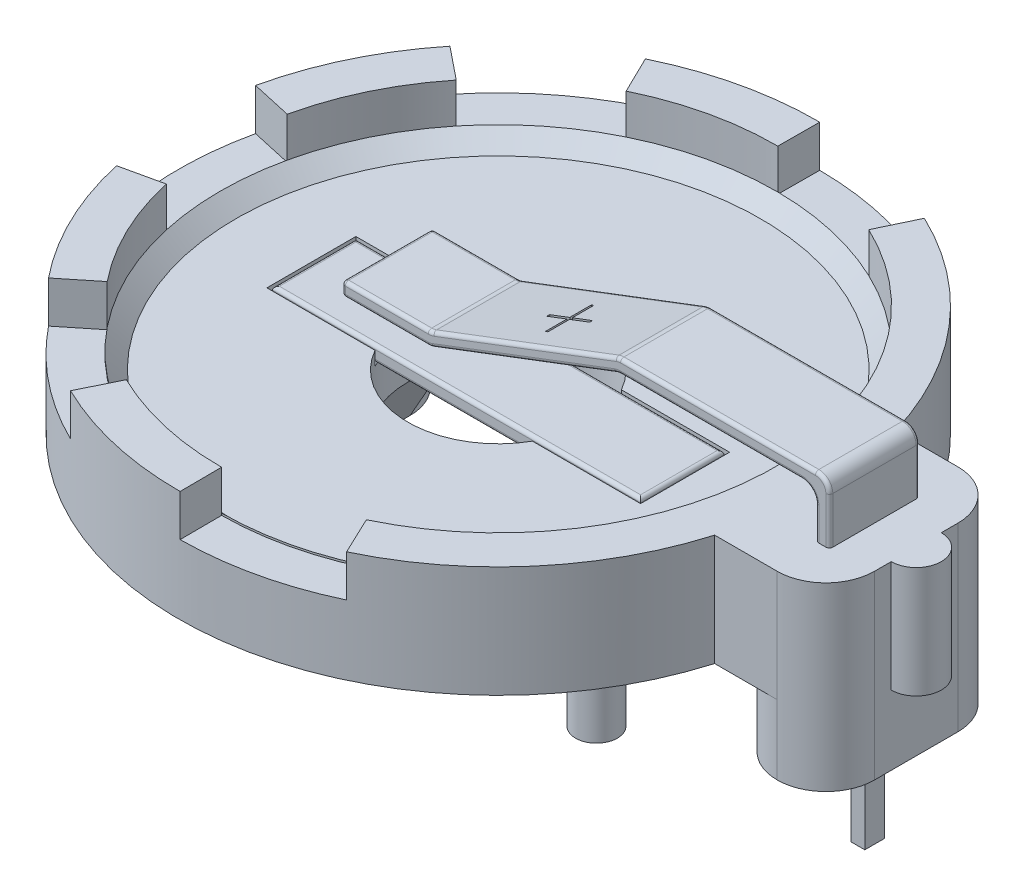
SolidWorks part; units mm, degrees
ref_plane "Front Plane" through (0, 0, 0) normal (0, 0, 1) x (1, 0, 0)
ref_plane "Top Plane" through (0, 0, 0) normal (0, 1, 0) x (1, 0, 0)
ref_plane "Right Plane" through (0, 0, 0) normal (1, 0, 0) x (0, 0, -1)
sketch "Sketch3" plane through (0, 0, 0) normal (0, 1, 0) x (1, 0, 0)
  line L0 (0, 0) -> (24.2923, 0) construction
  line L1 (11.0312, 3.25) -> (11.0312, -3.25) construction
  line L2 (15.0312, -3.25) -> (11.0312, -3.25)
  line L3 (15.0312, -3.25) -> (15.0312, 3.25)
  line L4 (15.0312, 3.25) -> (11.0312, 3.25)
  line L5 (0, -11.5) -> (0, 11.5) construction
  line L6 (15.0312, -3.25) -> (11.0312, 3.25) construction
  line L7 (15.0312, 3.25) -> (11.0312, -3.25) construction
  circle A0 centre (0, 0) radius 11.5 construction
  arc A1 (11.0312, 3.25) -> (11.0312, -3.25) centre (0, 0) ccw
  circle A2 centre (0, 0) radius 3.25
  point P3 (13.0312, 0)
  dimension "D1" = 23
  dimension "D4" = 6.5
  dimension "D2" = 4
  dimension "D3" = 6.5
extrude "Boss-Extrude2" add sketch "Sketch3" along normal blind 4
sketch "Sketch7" plane through (0, 4, 0) normal (0, 1, 0) x (1, 0, 0)
  circle A0 centre (0, 0) radius 10
  dimension "D1" = 20
extrude "Cut-Extrude1" cut sketch "Sketch7" against normal blind 2
chamfer "Chamfer3" distance 0.57 angle 45 1 edges at (0, 2, 10)
sketch "Sketch8" plane through (0, 4, 0) normal (0, 1, 0) x (1, 0, 0)
  line L0 (-11.5, 0) -> (-10, 0) construction
  line L1 (-9.7608, 2.1739) -> (-11.225, 2.5) construction
  line L2 (-9.7608, -2.1739) -> (-11.225, -2.5) construction
  line L3 (-11.225, 2.5) -> (-11.225, -2.5) construction
  line L4 (-11.225, 2.5) -> (-9.7608, 2.1739)
  line L5 (-11.225, -2.5) -> (-9.7608, -2.1739)
  line L6 (-5.0441, 10.3348) -> (-4.3862, 8.9867)
  line L7 (-8.9532, 7.2173) -> (-7.7854, 6.2759)
  line L8 (4.9351, 10.3872) -> (4.2914, 9.0324)
  line L9 (0.0605, 11.4998) -> (0.0526, 9.9999)
  line L10 (11.1981, 2.6179) -> (9.7374, 2.2764) [skipped]
  line L11 (9.0286, 7.1228) -> (7.851, 6.1937) [skipped]
  line L12 (9.0286, -7.1228) -> (7.851, -6.1937) [skipped]
  line L13 (11.1981, -2.6179) -> (9.7374, -2.2764) [skipped]
  line L14 (0.0605, -11.4998) -> (0.0526, -9.9999)
  line L15 (4.9351, -10.3872) -> (4.2914, -9.0324)
  line L16 (-8.9532, -7.2173) -> (-7.7854, -6.2759)
  line L17 (-5.0441, -10.3348) -> (-4.3862, -8.9867)
  arc A0 (11.0312, 3.25) -> (11.0312, -3.25) centre (0, 0) ccw construction
  circle A2 centre (0, 0) radius 10 construction
  arc A3 (-9.7608, 2.1739) -> (-9.7608, -2.1739) centre (0, 0) ccw
  arc A4 (-11.225, 2.5) -> (-11.225, -2.5) centre (0, 0) ccw
  arc A5 (-4.3862, 8.9867) -> (-7.7854, 6.2759) centre (0, 0) ccw
  arc A6 (-5.0441, 10.3348) -> (-8.9532, 7.2173) centre (0, 0) ccw
  arc A7 (4.2914, 9.0324) -> (0.0526, 9.9999) centre (0, 0) ccw
  arc A8 (4.9351, 10.3872) -> (0.0605, 11.4998) centre (0, 0) ccw
  arc A9 (9.7374, 2.2764) -> (7.851, 6.1937) centre (0, 0) ccw [skipped]
  arc A10 (11.1981, 2.6179) -> (9.0286, 7.1228) centre (0, 0) ccw [skipped]
  arc A11 (7.851, -6.1937) -> (9.7374, -2.2764) centre (0, 0) ccw [skipped]
  arc A12 (9.0286, -7.1228) -> (11.1981, -2.6179) centre (0, 0) ccw [skipped]
  arc A13 (0.0526, -9.9999) -> (4.2914, -9.0324) centre (0, 0) ccw
  arc A14 (0.0605, -11.4998) -> (4.9351, -10.3872) centre (0, 0) ccw
  arc A15 (-7.7854, -6.2759) -> (-4.3862, -8.9867) centre (0, 0) ccw
  arc A16 (-8.9532, -7.2173) -> (-5.0441, -10.3348) centre (0, 0) ccw
  dimension "D1" = 5
  dimension "D2" = 7
extrude "Cut-Extrude2" cut sketch "Sketch8" against normal blind 1.5
sketch "Sketch9" plane through (0, 0, 0) normal (0, -1, 0) x (1, 0, 0)
  line L1 (15.0312, -3.25) -> (11.0312, -3.25) construction
  line L2 (15.0312, 3.25) -> (11.5312, 3.25)
  line L3 (15.0312, 3.25) -> (15.0312, -3.25)
  line L4 (15.0312, -3.25) -> (11.5312, -3.25)
  line L6 (11.5312, 3.25) -> (11.5312, -3.25)
  line L7 (0, 0) -> (-7.9407, 0) construction
  line L8 (0, 11.5) -> (0, -11.5) construction
  line L9 (-8.1688, 3.25) -> (-4.6688, 3.25)
  line L10 (-8.1688, 3.25) -> (-8.1688, -3.25)
  line L11 (-8.1688, -3.25) -> (-4.6688, -3.25)
  line L12 (-4.6688, 3.25) -> (-4.6688, -3.25)
  line L13 (-8.1688, 3.25) -> (-4.6688, -3.25) construction
  line L14 (-8.1688, -3.25) -> (-4.6688, 3.25) construction
  arc A0 (11.0312, 3.25) -> (11.0312, -3.25) centre (0, 0) ccw construction
  circle A1 centre (0, -9.65) radius 0.75
  circle A2 centre (-8.3571, 4.825) radius 0.75
  circle A3 centre (8.3571, 4.825) radius 0.75
  point P9 (-6.4188, 0)
  dimension "D5" = 1.5
  dimension "D1" = 3.5
  dimension "D2" = 3.5
  dimension "D3" = 23.2
  dimension "D4" = 6.5
  dimension "D6" = 1.85
  dimension "D7" = 3
extrude "Boss-Extrude6" add sketch "Sketch9" along normal blind 2.5
fillet "Fillet1" radius 1.75 8 edges at (15.0312, 0.75, -3.25) (15.0312, 0.75, 3.25) (-4.6688, -1.25, -3.25) (-8.1688, -1.25, -3.25) (-4.6688, -1.25, 3.25) (-8.1688, -1.25, 3.25)
sketch "Sketch10" plane through (0, 0, 0) normal (0, 0, 1) x (1, 0, 0)
  line L1 (11.5312, -2.5) -> (13.2812, -2.5) construction
  line L3 (11.5312, 0) -> (10.2312, 0) construction
  line L4 (11.5312, 0) -> (11.5312, -2.5) construction
  line L5 (11.5312, -2.5) -> (10.2312, -2.5) construction
  line L6 (10.2312, 0) -> (10.2312, -2.5) construction
  line L7 (10.2312, 0) -> (11.5312, -2.5)
  dimension "D1" = 1.3
rib "Rib1" sketch "Sketch10" sketch "Sketch10" thickness 3 extrusion direction parallel to sketch draft on no parameters "D1"=3
sketch "Sketch12" plane through (0, 0, 0) normal (0, 0, 1) x (1, 0, 0)
  line L0 (-6.4188, -2.5) -> (-4.6688, -2.5) construction
  line L1 (-3.25, 0) -> (-4.6688, 0) construction
  line L2 (-3.25, 0) -> (-3.25, -2.5) construction
  line L3 (-3.25, -2.5) -> (-4.6688, -2.5) construction
  line L4 (-4.6688, 0) -> (-4.6688, -2.5) construction
  line L5 (-4.6688, 0) -> (-4.6688, -2.5) construction
  line L6 (-3.25, 0) -> (-4.6688, -2.5)
rib "Rib2" sketch "Sketch12" sketch "Sketch12" thickness 3 extrusion direction parallel to sketch draft on no parameters "D1"=3
sketch "Sketch13" plane through (0, -2.5, 0) normal (0, -1, 0) x (1, 0, 0)
  line L0 (13.2812, 3.25) -> (13.2812, -3.25) construction
  line L1 (15.0312, 0) -> (-8.1688, 0) construction
  line L2 (15.0312, -1.5) -> (15.0312, 1.5) construction
  line L3 (-8.1688, 1.5) -> (-8.1688, -1.5) construction
  line L4 (-6.9688, 0.35) -> (-6.4688, 0.35)
  line L5 (13.0312, 0.35) -> (13.5312, 0.35)
  line L6 (13.0312, 0.35) -> (13.0312, -0.35)
  line L7 (13.0312, -0.35) -> (13.5312, -0.35)
  line L8 (13.5312, 0.35) -> (13.5312, -0.35)
  line L9 (13.0312, 0.35) -> (13.5312, -0.35) construction
  line L10 (13.0312, -0.35) -> (13.5312, 0.35) construction
  line L11 (-6.9688, -0.35) -> (-6.4688, -0.35)
  line L12 (-6.4688, 0.35) -> (-6.4688, -0.35)
  line L13 (-6.9688, 0.35) -> (-6.9688, -0.35)
  line L14 (-6.9688, -0.35) -> (-6.4688, 0.35) construction
  line L15 (-6.9688, 0.35) -> (-6.4688, -0.35) construction
  point P10 (13.2812, 0)
  point P15 (-6.7188, 0)
  dimension "D1" = 0.7
  dimension "D2" = 0.5
  dimension "D3" = 2
extrude "Boss-Extrude7" add sketch "Sketch13" along normal blind 3.5 separate body
sketch "Sketch14" plane through (0, 2, 0) normal (0, 1, 0) x (1, 0, 0)
  line L0 (-6.9688, 0.35) -> (-6.4688, 0.35) construction
  line L1 (-6.9688, -0.35) -> (-6.9688, 0.35) construction
  line L2 (-6.4688, -0.35) -> (-6.9688, -0.35) construction
  line L3 (-6.4688, 0.35) -> (-6.4688, -0.35) construction
  line L8 (-6.9688, 0.35) -> (-6.4688, 0.35) construction
  line L9 (-6.9688, -0.35) -> (-6.9688, 0.35) construction
  line L10 (-6.4688, -0.35) -> (-6.9688, -0.35) construction
  line L11 (-6.4688, 0.35) -> (-6.4688, -0.35) construction
  line L12 (-6.9688, 0.35) -> (-6.4688, -0.35) construction
  line L13 (2.8289, 1.6) -> (6.7189, 1.6)
  line L14 (2.8289, 1.6) -> (2.8289, -1.6) construction
  line L15 (2.8289, -1.6) -> (6.7189, -1.6)
  line L16 (-11.5, 0) -> (15.0312, 0) construction
  line L17 (15.0312, -1.5) -> (15.0312, 1.5) construction
  line L18 (6.7189, 1.6) -> (6.7189, -1.6)
  line L19 (2.8289, 1.6) -> (6.7189, -1.6) construction
  line L20 (2.8289, -1.6) -> (6.7189, 1.6) construction
  line L21 (-6.7188, 1.6) -> (-2.8289, 1.6)
  line L22 (-6.7188, 1.6) -> (-6.7188, -1.6)
  line L23 (-6.7188, -1.6) -> (-2.8289, -1.6)
  line L24 (-2.8289, 1.6) -> (-2.8289, -1.6) construction
  line L25 (-6.7188, 1.6) -> (-2.8289, -1.6) construction
  line L26 (-6.7188, -1.6) -> (-2.8289, 1.6) construction
  line L27 (-6.9688, -0.35) -> (-6.4688, 0.35) construction
  arc A0 (-11.225, 2.5) -> (-11.225, -2.5) centre (0, 0) ccw construction
  circle A1 centre (0, 0) radius 3.25 construction
  arc A2 (-2.8289, 1.6) -> (-2.8289, -1.6) centre (0, 0) ccw
  arc A3 (2.8289, -1.6) -> (2.8289, 1.6) centre (0, 0) ccw
  point P4 (4.7739, 0)
  point P18 (-4.7738, 0)
  point P23 (-6.7188, 0)
  dimension "D1" = 3.2
  dimension "D2" = 3.89
  dimension "D3" = 3.2
extrude "Cut-Extrude3" cut sketch "Sketch14" against normal blind 0.5
sketch "Sketch15" plane through (0, 1.5, 0) normal (0, 1, 0) x (1, 0, 0)
  line L0 (-2.8289, 1.6) -> (-6.7188, 1.6) construction
  line L1 (-6.6188, 1.5) -> (6.6189, 1.5)
  line L2 (-6.6188, 1.5) -> (-6.6188, -1.5)
  line L3 (-6.6188, -1.5) -> (6.6189, -1.5)
  line L4 (6.6189, 1.5) -> (6.6189, -1.5)
  line L5 (-6.7188, 1.6) -> (-6.7188, -1.6) construction
  line L6 (-6.7188, -1.6) -> (-2.8289, -1.6) construction
  line L7 (6.7189, -1.6) -> (6.7189, 1.6) construction
  dimension "D1" = 0.1
  dimension "D2" = 0.1
  dimension "D3" = 0.1
  dimension "D4" = 0.1
extrude "Boss-Extrude8" add sketch "Sketch15" along normal blind 0.55 separate body
sketch "Sketch16" plane through (0, 0, 0) normal (0, 0, 1) x (1, 0, 0)
  line L0 (13.5312, -6) -> (13.0312, -6) construction
  line L1 (13.5312, -6) -> (13.0312, -6) construction
  line L2 (13.2812, -6) -> (13.2812, 9.6729) construction
  line L3 (13.2812, 5.67) -> (5.9312, 5.67) construction
  line L4 (13.2812, 6.17) -> (5.9312, 6.17)
  line L5 (11.0312, 4) -> (13.2812, 4) construction
  line L6 (5.9312, 6.17) -> (-0.799, 3.6118)
  line L7 (13.5312, 4) -> (13.0312, 4)
  line L8 (13.5312, 4) -> (13.5312, 6.17)
  line L9 (13.5312, 6.17) -> (13.0312, 6.17) construction
  line L10 (13.0312, 4) -> (13.0312, 6.17) construction
  line L11 (13.5312, 4) -> (13.0312, 6.17) construction
  line L12 (13.5312, 6.17) -> (13.0312, 4) construction
  line L13 (5.9312, 5.67) -> (-0.799, 3.1118)
  line L14 (-0.799, 3.6118) -> (-3.999, 3.6118)
  line L15 (-3.999, 3.6118) -> (-3.999, 3.1118)
  line L16 (-3.999, 3.1118) -> (-0.799, 3.1118)
  line L17 (5.9312, 5.67) -> (13.0312, 5.67)
  line L18 (13.0312, 5.67) -> (13.0312, 4)
  line L20 (13.2812, 6.17) -> (13.5312, 6.17)
  point P10 (12.1562, 4)
  point P11 (13.2812, 5.085)
  dimension "D1" = 1.67
  dimension "D2" = 0.5
  dimension "D3" = 0.5
  dimension "D4" = 7.6
  dimension "D5" = 0.5
  dimension "D6" = 7.2
  dimension "D7" = 0.5
  dimension "D8" = 3.2
  dimension "D9" = 20.812
  dimension "D10" = 20.812
extrude "Boss-Extrude9" add sketch "Sketch16" along normal mid plane 3.25 separate body
fillet "Fillet2" radius 0.5 6 edges at (-0.799, 3.1118, 0) (-0.799, 3.6118, 0) (5.9312, 5.67, 0) (5.9312, 6.17, 0) (13.0312, 5.67, 0) (13.5312, 6.17, 0)
fillet "Fillet3" radius 0.125 32 edges at (13.0312, 4.585, 1.625) (12.8848, 5.5236, 1.625) (9.2771, 5.67, 1.625) (5.9327, 5.6618, 1.625) (2.5661, 4.3909, 1.625) (-0.8005, 3.1201, 1.625) (13.0312, 4.585, -1.625) (12.8848, 5.5236, -1.625) (9.2771, 5.67, -1.625) (5.9327, 5.6618, -1.625) (2.5661, 4.3909, -1.625) (-0.8005, 3.1201, -1.625) (13.5312, 4.835, -1.625) (13.3848, 6.0236, -1.625) (9.5271, 6.17, -1.625) (5.9327, 6.1618, -1.625) (2.5661, 4.8909, -1.625) (-0.8005, 3.6201, -1.625) (13.5312, 4.835, 1.625) (13.3848, 6.0236, 1.625) (9.5271, 6.17, 1.625) (5.9327, 6.1618, 1.625) (2.5661, 4.8909, 1.625) (-0.8005, 3.6201, 1.625) (-3.999, 3.1118, 0) (-2.4449, 3.1118, 1.625) (-2.4449, 3.1118, -1.625) (-3.999, 3.6118, 0) (-2.4449, 3.6118, -1.625) (-2.4449, 3.6118, 1.625) (-3.999, 3.3618, -1.625) (-3.999, 3.3618, 1.625)
fillet "Fillet4" radius 0.125 8 edges at (0, 1.5, 1.5) (6.6189, 1.5, 0) (0, 1.5, -1.5) (-6.6188, 1.5, 0) (0, 2.05, -1.5) (6.6189, 2.05, 0) (0, 2.05, 1.5) (-6.6188, 2.05, 0)
sketch "Sketch18" plane through (-1.3004, 3.4213, 0) normal (-0.3553, 0.9348, 0) x (0.9348, 0.3553, 0)
  line L0 (-999.3718, 0) -> (49000.6282, 0) construction
  line L1 (0.6282, 1.5) -> (0.6282, -1.5) construction
  line L2 (4.1364, -998.5) -> (4.1364, 49001.5) construction
  line L3 (7.6446, 1.5) -> (0.6282, 1.5) construction
  line L4 (4.0864, 0.05) -> (3.3114, 0.05)
  line L5 (4.0864, 0.825) -> (4.1864, 0.825) construction
  line L6 (4.0864, 0.825) -> (4.0864, -0.825) construction
  line L7 (4.0864, -0.825) -> (4.1864, -0.825) construction
  line L8 (4.1864, 0.825) -> (4.1864, -0.825) construction
  line L9 (4.0864, 0.825) -> (4.1864, -0.825) construction
  line L10 (4.0864, -0.825) -> (4.1864, 0.825) construction
  line L11 (3.3114, 0.05) -> (4.9614, 0.05) construction
  line L12 (3.3114, 0.05) -> (3.3114, -0.05) construction
  line L13 (3.3114, -0.05) -> (4.9614, -0.05) construction
  line L14 (4.9614, 0.05) -> (4.9614, -0.05) construction
  line L15 (3.3114, 0.05) -> (4.9614, -0.05) construction
  line L16 (3.3114, -0.05) -> (4.9614, 0.05) construction
  line L17 (3.3114, 0.05) -> (3.3114, -0.05)
  line L18 (3.3114, -0.05) -> (4.0864, -0.05)
  line L19 (4.0864, -0.05) -> (4.0864, -0.825)
  line L20 (4.0864, -0.825) -> (4.1864, -0.825)
  line L21 (4.1864, -0.825) -> (4.1864, -0.05)
  line L22 (4.9614, 0.05) -> (4.1864, 0.05)
  line L23 (4.1864, 0.05) -> (4.1864, 0.825)
  line L24 (4.1864, 0.825) -> (4.0864, 0.825)
  line L25 (4.0864, 0.825) -> (4.0864, 0.05)
  line L26 (4.9614, 0.05) -> (4.9614, -0.05)
  line L27 (4.9614, -0.05) -> (4.1864, -0.05)
  point P5 (0.6282, 0)
  point P6 (4.1364, 0)
  point P10 (4.1364, 1.5)
  point P15 (4.1364, 0)
  dimension "D1" = 1.65
  dimension "D2" = 1.65
  dimension "D3" = 0.1
  dimension "D4" = 0.1
extrude "Cut-Extrude4" cut sketch "Sketch18" against normal blind 0.125
sketch "Sketch20" plane through (0, 4, 0) normal (0, 1, 0) x (1, 0, 0)
  line L0 (15.0312, -1.5) -> (15.0312, 1.5) construction
  line L1 (15.0312, -1.5) -> (15.0312, 1.5) construction
  line L2 (15.0312, 0.9) -> (15.0312, -0.9)
  arc A0 (15.0312, 0.9) -> (15.0312, -0.9) centre (15.0312, 0) cw
  dimension "D1" = 0.9
extrude "Boss-Extrude10" add sketch "Sketch20" against normal blind 4
